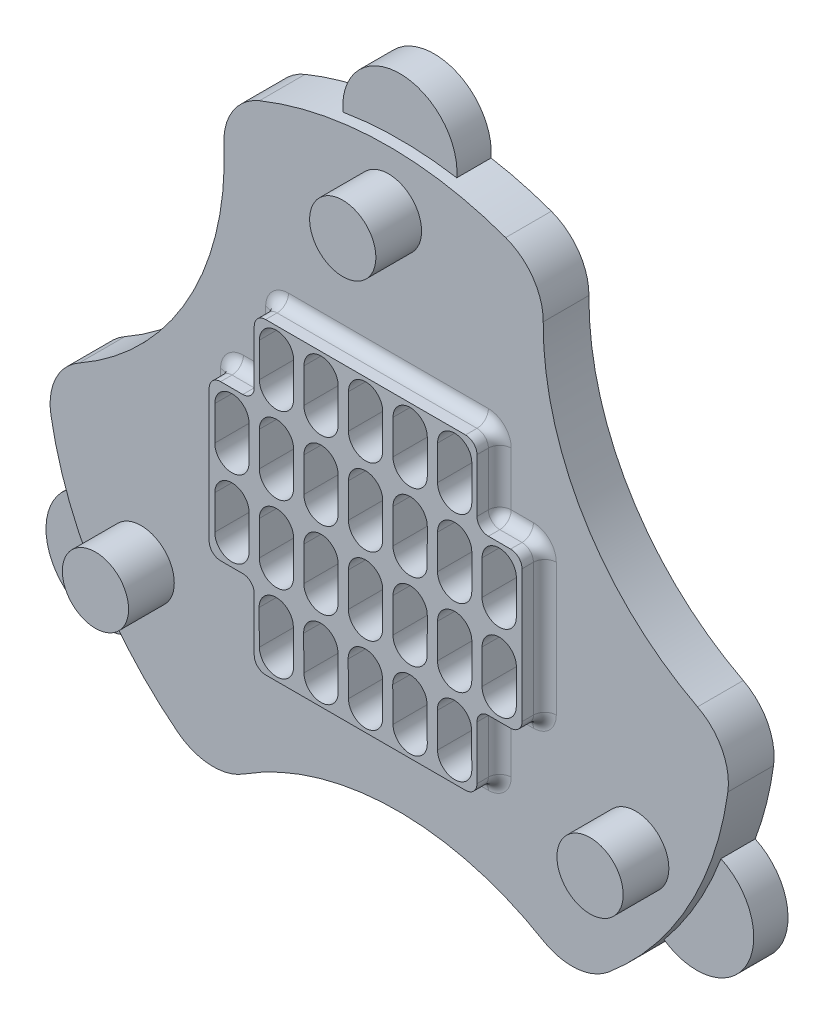
SolidWorks part; units mm, degrees
ref_plane "Спереди" through (0, 0, 0) normal (0, 0, 1) x (1, 0, 0)
ref_plane "Сверху" through (0, 0, 0) normal (0, 1, 0) x (1, 0, 0)
ref_plane "Справа" through (0, 0, 0) normal (1, 0, 0) x (0, 0, -1)
sketch "Sketch1" plane through (0, 0, 0) normal (0, 0, 1) x (1, 0, 0)
  line L0 (3.9, 6.755) -> (7.8, 0) construction
  line L2 (5.85, 10.1325) -> (11.7, 0) construction
  line L4 (7.8, 13.51) -> (15.6, 0) construction
  circle A61 centre (0, 0) radius 20
  circle A131 centre (0, 0) radius 1.25
  circle A484 centre (3.9, 0) radius 1.25
  circle A485 centre (7.8, 0) radius 1.25
  circle A486 centre (11.7, 0) radius 1.25
  circle A487 centre (15.6, 0) radius 1.25
  circle A488 centre (1.95, -3.3775) radius 1.25
  circle A489 centre (3.9, -6.755) radius 1.25
  circle A490 centre (5.85, -10.1325) radius 1.25
  circle A491 centre (7.8, -13.51) radius 1.25
  circle A492 centre (-1.95, -3.3775) radius 1.25
  circle A493 centre (-3.9, -6.755) radius 1.25
  circle A494 centre (-5.85, -10.1325) radius 1.25
  circle A495 centre (-7.8, -13.51) radius 1.25
  circle A496 centre (-3.9, 0) radius 1.25
  circle A497 centre (-7.8, 0) radius 1.25
  circle A498 centre (-11.7, 0) radius 1.25
  circle A499 centre (-15.6, 0) radius 1.25
  circle A500 centre (-1.95, 3.3775) radius 1.25
  circle A501 centre (-3.9, 6.755) radius 1.25
  circle A502 centre (-5.85, 10.1325) radius 1.25
  circle A503 centre (-7.8, 13.51) radius 1.25
  circle A504 centre (1.95, 3.3775) radius 1.25
  circle A505 centre (3.9, 6.755) radius 1.25
  circle A506 centre (5.85, 10.1325) radius 1.25
  circle A507 centre (7.8, 13.51) radius 1.25
  circle A508 centre (5.85, 3.3775) radius 1.25
  circle A509 centre (7.8, 6.755) radius 1.25
  circle A510 centre (9.75, 3.3775) radius 1.25
  circle A511 centre (11.7, 6.755) radius 1.25
  circle A512 centre (9.7491, 10.1341) radius 1.25
  circle A513 centre (13.6509, 3.3759) radius 1.25
  circle A514 centre (5.85, -3.3791) radius 1.25
  circle A515 centre (9.75, -3.3791) radius 1.25
  circle A516 centre (7.8, -6.7566) radius 1.25
  circle A517 centre (11.7, -6.7566) radius 1.25
  circle A518 centre (9.7491, -10.1356) radius 1.25
  circle A519 centre (13.6509, -3.3775) radius 1.25
  circle A520 centre (-0.0013, -6.7573) radius 1.25
  circle A521 centre (1.9487, -10.1348) radius 1.25
  circle A522 centre (-1.9513, -10.1348) radius 1.25
  circle A523 centre (-0.0013, -13.5123) radius 1.25
  circle A524 centre (-3.9032, -13.5123) radius 1.25
  circle A525 centre (3.9005, -13.5123) radius 1.25
  circle A526 centre (-5.8527, -3.3791) radius 1.25
  circle A527 centre (-7.8027, -6.7566) radius 1.25
  circle A528 centre (-9.7527, -3.3791) radius 1.25
  circle A529 centre (-11.7027, -6.7566) radius 1.25
  circle A530 centre (-13.6536, -3.3775) radius 1.25
  circle A531 centre (-9.7518, -10.1356) radius 1.25
  circle A532 centre (-5.8527, 3.3775) radius 1.25
  circle A533 centre (-9.7527, 3.3775) radius 1.25
  circle A534 centre (-7.8027, 6.755) radius 1.25
  circle A535 centre (-11.7027, 6.755) radius 1.25
  circle A536 centre (-9.7518, 10.1341) radius 1.25
  circle A537 centre (-13.6536, 3.3759) radius 1.25
  circle A538 centre (-0.0014, 6.7558) radius 1.25
  circle A539 centre (-1.9514, 10.1333) radius 1.25
  circle A540 centre (1.9486, 10.1333) radius 1.25
  circle A541 centre (-0.0014, 13.5108) radius 1.25
  circle A542 centre (3.9005, 13.5108) radius 1.25
  circle A543 centre (-3.9032, 13.5108) radius 1.25
  circle A544 centre (13.65, -1.1258) radius 2.2517 construction
  circle A545 centre (11.7009, -4.5044) radius 2.2522 construction
  circle A546 centre (9.75, -7.8834) radius 2.2522 construction
  circle A547 centre (7.7987, -11.2591) radius 2.2509 construction
  circle A548 centre (13.65, -1.1258) radius 0.65
  circle A549 centre (11.7009, -4.5044) radius 0.65
  circle A550 centre (9.75, -7.8834) radius 0.65
  circle A551 centre (7.7987, -11.2591) radius 0.65
  circle A552 centre (9.75, -1.1258) radius 0.65
  circle A553 centre (7.8009, -4.5044) radius 0.65
  circle A554 centre (5.85, -7.8834) radius 0.65
  circle A555 centre (3.8987, -11.2591) radius 0.65
  circle A556 centre (5.85, -1.1258) radius 0.65
  circle A557 centre (3.9009, -4.5044) radius 0.65
  circle A558 centre (1.95, -7.8834) radius 0.65
  circle A559 centre (-0.0013, -11.2591) radius 0.65
  circle A560 centre (1.95, -1.1258) radius 0.65
  circle A561 centre (0.0009, -4.5044) radius 0.65
  circle A562 centre (-1.95, -7.8834) radius 0.65
  circle A563 centre (-3.9013, -11.2591) radius 0.65
  circle A564 centre (-1.95, -1.1258) radius 0.65
  circle A565 centre (-3.8991, -4.5044) radius 0.65
  circle A566 centre (-5.85, -7.8834) radius 0.65
  circle A567 centre (-7.8013, -11.2591) radius 0.65
  circle A568 centre (-5.85, -1.1258) radius 0.65
  circle A569 centre (-7.7991, -4.5044) radius 0.65
  circle A570 centre (-9.75, -7.8834) radius 0.65
  circle A572 centre (-9.75, -1.1258) radius 0.65
  circle A573 centre (-11.6991, -4.5044) radius 0.65
  circle A576 centre (-13.65, -1.1258) radius 0.65
  circle A587 centre (0, 2.2517) radius 2.2517 construction
  circle A588 centre (0, 2.2517) radius 0.65
  circle A589 centre (3.9, 2.2517) radius 0.65
  circle A590 centre (7.8, 2.2517) radius 0.65
  circle A591 centre (11.7, 2.2517) radius 0.65
  circle A592 centre (15.6, 2.2517) radius 0.65
  circle A593 centre (1.9491, 5.6297) radius 2.2522 construction
  circle A594 centre (1.9491, 5.6297) radius 0.65
  circle A595 centre (5.8491, 5.6297) radius 0.65
  circle A596 centre (9.7491, 5.6297) radius 0.65
  circle A597 centre (13.6491, 5.6297) radius 0.65
  circle A598 centre (3.8991, 9.0072) radius 2.2522 construction
  circle A599 centre (3.8991, 9.0072) radius 0.65
  circle A600 centre (7.7991, 9.0072) radius 0.65
  circle A601 centre (11.6991, 9.0072) radius 0.65
  circle A602 centre (5.85, 12.3842) radius 2.2517 construction
  circle A603 centre (5.85, 12.3842) radius 0.65
  circle A604 centre (9.75, 12.3842) radius 0.65
  circle A605 centre (5.85, -14.6358) radius 0.65
  circle A606 centre (1.9509, -14.6353) radius 0.65
  circle A607 centre (-1.9491, -14.6353) radius 0.65
  circle A608 centre (-5.85, -14.6358) radius 0.65
  circle A609 centre (-15.6, 2.2517) radius 0.65
  circle A610 centre (-13.65, 5.6281) radius 0.65
  circle A611 centre (-11.7, 9.0056) radius 0.65
  circle A612 centre (-9.75, 12.3842) radius 0.65
  circle A613 centre (-5.85, 12.3842) radius 0.65
  circle A614 centre (-1.95, 12.3842) radius 0.65
  circle A615 centre (1.95, 12.3842) radius 0.65
  circle A616 centre (-7.8, 9.0056) radius 0.65
  circle A617 centre (-9.75, 5.6281) radius 0.65
  circle A618 centre (-11.7, 2.2517) radius 0.65
  circle A619 centre (-3.9, 9.0056) radius 0.65
  circle A620 centre (-5.85, 5.6281) radius 0.65
  circle A621 centre (-7.8, 2.2517) radius 0.65
  circle A622 centre (0, 9.0056) radius 0.65
  circle A623 centre (-1.95, 5.6281) radius 0.65
  circle A624 centre (-3.9, 2.2517) radius 0.65
  circle A625 centre (-15.5991, -4.5044) radius 0.65
  circle A626 centre (-13.65, -7.8834) radius 0.65
  circle A627 centre (-17.55, -7.8834) radius 0.65
  circle A628 centre (-19.5013, -11.2591) radius 0.65
  circle A629 centre (-15.6013, -11.2591) radius 0.65
  circle A630 centre (-11.7013, -11.2591) radius 0.65
  point P51 (0, 0)
  point P125 (-0.0013, -0.0008)
  point P231 (0, 0)
  dimension "D1" = 5
  dimension "D3" = 6
  dimension "D5" = 8
  dimension "D7" = 4
  dimension "D11" = 4
  dimension "D2" = 6
  dimension "D6" = 5
  dimension "D8" = 3
  dimension "D9" = 2
  dimension "D4" = 1.3
  dimension "D10" = 3
ref_plane "Plane1" through (0, 0, 10) normal (0, 0, 1) x (1, 0, 0)
sketch "Sketch2" plane through (0, 0, 10) normal (0, 0, 1) x (1, 0, 0)
  line L0 (-7.8, 13.51) -> (-7.8027, 6.755) construction
  line L1 (-9.7518, 10.1341) -> (-5.85, 10.1325) construction
  line L2 (-7.8008, 11.6325) -> (-7.8019, 8.6325) construction
  line L3 (-6.3008, 11.6319) -> (-6.3019, 8.6319)
  line L4 (-9.3008, 11.6331) -> (-9.3019, 8.6331)
  line L5 (-5.4008, 11.6331) -> (-5.4019, 8.6331)
  line L6 (-2.4008, 11.6319) -> (-2.4019, 8.6319)
  line L7 (-3.9008, 11.6325) -> (-3.9019, 8.6325) construction
  line L8 (-1.5008, 11.6331) -> (-1.5019, 8.6331)
  line L9 (1.4992, 11.6319) -> (1.4981, 8.6319)
  line L10 (-0.0008, 11.6325) -> (-0.0019, 8.6325) construction
  line L11 (2.3992, 11.6331) -> (2.3981, 8.6331)
  line L12 (5.3992, 11.6319) -> (5.3981, 8.6319)
  line L13 (3.8992, 11.6325) -> (3.8981, 8.6325) construction
  line L14 (6.2992, 11.6331) -> (6.2981, 8.6331)
  line L15 (9.2992, 11.6319) -> (9.2981, 8.6319)
  line L16 (7.7992, 11.6325) -> (7.7981, 8.6325) construction
  line L17 (-9.7518, 10.1341) -> (-9.7527, 3.3775) construction
  line L18 (-11.7027, 6.755) -> (-7.8027, 6.755) construction
  line L19 (-10.2035, 1.8767) -> (-10.202, 4.8767)
  line L22 (-9.7527, 3.3775) -> (-5.8527, 3.3775) construction
  line L25 (-7.8027, 6.755) -> (-7.8, 0) construction
  line L26 (-7.8035, 1.8775) -> (-7.8019, 4.8775) construction
  line L27 (-9.3035, 1.8782) -> (-9.3019, 4.8782)
  line L28 (-6.3035, 1.8767) -> (-6.3019, 4.8767)
  line L29 (-2.4035, 1.8767) -> (-2.4019, 4.8767)
  line L30 (-5.4035, 1.8782) -> (-5.4019, 4.8782)
  line L31 (-3.9035, 1.8775) -> (-3.9019, 4.8775) construction
  line L32 (1.4965, 1.8767) -> (1.4981, 4.8767)
  line L33 (-1.5035, 1.8782) -> (-1.5019, 4.8782)
  line L34 (-0.0035, 1.8775) -> (-0.0019, 4.8775) construction
  line L35 (5.3965, 1.8767) -> (5.3981, 4.8767)
  line L36 (2.3965, 1.8782) -> (2.3981, 4.8782)
  line L37 (3.8965, 1.8775) -> (3.8981, 4.8775) construction
  line L38 (9.2965, 1.8767) -> (9.2981, 4.8767)
  line L39 (6.2965, 1.8782) -> (6.2981, 4.8782)
  line L40 (7.7965, 1.8775) -> (7.7981, 4.8775) construction
  line L41 (13.1965, 1.8767) -> (13.1981, 4.8767)
  line L42 (10.1965, 1.8782) -> (10.1981, 4.8782)
  line L43 (11.6965, 1.8775) -> (11.6981, 4.8775) construction
  line L44 (-13.2035, 1.8782) -> (-13.2019, 4.8782)
  line L45 (-11.7035, 1.8775) -> (-11.702, 4.8775) construction
  line L46 (-9.7527, -3.3791) -> (-5.8527, -3.3791) construction
  line L47 (-7.8, 0) -> (-7.8027, -6.7566) construction
  line L48 (-7.8046, -4.8791) -> (-7.8008, -1.8791) construction
  line L49 (-9.3046, -4.8771) -> (-9.3007, -1.8771)
  line L50 (-6.3047, -4.881) -> (-6.3008, -1.881)
  line L51 (-2.4047, -4.881) -> (-2.4008, -1.881)
  line L52 (-5.4046, -4.8771) -> (-5.4007, -1.8771)
  line L53 (-3.9046, -4.8791) -> (-3.9008, -1.8791) construction
  line L54 (1.4953, -4.881) -> (1.4992, -1.881)
  line L55 (-1.5046, -4.8771) -> (-1.5007, -1.8771)
  line L56 (-0.0046, -4.8791) -> (-0.0008, -1.8791) construction
  line L57 (5.3953, -4.881) -> (5.3992, -1.881)
  line L58 (2.3954, -4.8771) -> (2.3993, -1.8771)
  line L59 (3.8954, -4.8791) -> (3.8992, -1.8791) construction
  line L60 (9.2953, -4.881) -> (9.2992, -1.881)
  line L61 (6.2954, -4.8771) -> (6.2993, -1.8771)
  line L62 (7.7954, -4.8791) -> (7.7992, -1.8791) construction
  line L63 (13.1953, -4.881) -> (13.1992, -1.881)
  line L64 (10.1954, -4.8771) -> (10.1993, -1.8771)
  line L65 (11.6954, -4.8791) -> (11.6992, -1.8791) construction
  line L66 (-10.2047, -4.881) -> (-10.2008, -1.881)
  line L67 (-13.2046, -4.8771) -> (-13.2007, -1.8771)
  line L68 (-11.7046, -4.8791) -> (-11.7008, -1.8791) construction
  line L69 (-9.7518, -10.1356) -> (-5.482, -10.1356) construction
  line L70 (-7.8027, -6.7566) -> (-7.8, -13.51) construction
  line L71 (-7.8259, -8.6356) -> (-7.8007, -11.6356) construction
  line L72 (-6.3259, -8.623) -> (-6.3008, -11.623)
  line L73 (-9.3258, -8.6482) -> (-9.3007, -11.6482)
  line L74 (-5.4258, -8.6482) -> (-5.4007, -11.6482)
  line L75 (-2.4259, -8.623) -> (-2.4008, -11.623)
  line L76 (-3.9259, -8.6356) -> (-3.9007, -11.6356) construction
  line L77 (-1.5258, -8.6482) -> (-1.5007, -11.6482)
  line L78 (1.4741, -8.623) -> (1.4992, -11.623)
  line L79 (-0.0259, -8.6356) -> (-0.0007, -11.6356) construction
  line L80 (2.3742, -8.6482) -> (2.3993, -11.6482)
  line L81 (5.3741, -8.623) -> (5.3992, -11.623)
  line L82 (3.8741, -8.6356) -> (3.8993, -11.6356) construction
  line L83 (6.2742, -8.6482) -> (6.2993, -11.6482)
  line L84 (9.2741, -8.623) -> (9.2992, -11.623)
  line L85 (7.7741, -8.6356) -> (7.7993, -11.6356) construction
  arc A0 (-6.3008, 11.6319) -> (-9.3008, 11.6331) centre (-7.8008, 11.6325) ccw
  arc A1 (-9.3019, 8.6331) -> (-6.3019, 8.6319) centre (-7.8019, 8.6325) ccw
  arc A2 (-2.4008, 11.6319) -> (-5.4008, 11.6331) centre (-3.9008, 11.6325) ccw
  arc A3 (-5.4019, 8.6331) -> (-2.4019, 8.6319) centre (-3.9019, 8.6325) ccw
  arc A4 (1.4992, 11.6319) -> (-1.5008, 11.6331) centre (-0.0008, 11.6325) ccw
  arc A5 (-1.5019, 8.6331) -> (1.4981, 8.6319) centre (-0.0019, 8.6325) ccw
  arc A6 (5.3992, 11.6319) -> (2.3992, 11.6331) centre (3.8992, 11.6325) ccw
  arc A7 (2.3981, 8.6331) -> (5.3981, 8.6319) centre (3.8981, 8.6325) ccw
  arc A8 (9.2992, 11.6319) -> (6.2992, 11.6331) centre (7.7992, 11.6325) ccw
  arc A9 (6.2981, 8.6331) -> (9.2981, 8.6319) centre (7.7981, 8.6325) ccw
  arc A14 (-9.3035, 1.8782) -> (-6.3035, 1.8767) centre (-7.8035, 1.8775) ccw
  arc A15 (-6.3019, 4.8767) -> (-9.3019, 4.8782) centre (-7.8019, 4.8775) ccw
  arc A16 (-5.4035, 1.8782) -> (-2.4035, 1.8767) centre (-3.9035, 1.8775) ccw
  arc A17 (-2.4019, 4.8767) -> (-5.4019, 4.8782) centre (-3.9019, 4.8775) ccw
  arc A18 (-1.5035, 1.8782) -> (1.4965, 1.8767) centre (-0.0035, 1.8775) ccw
  arc A19 (1.4981, 4.8767) -> (-1.5019, 4.8782) centre (-0.0019, 4.8775) ccw
  arc A20 (2.3965, 1.8782) -> (5.3965, 1.8767) centre (3.8965, 1.8775) ccw
  arc A21 (5.3981, 4.8767) -> (2.3981, 4.8782) centre (3.8981, 4.8775) ccw
  arc A22 (6.2965, 1.8782) -> (9.2965, 1.8767) centre (7.7965, 1.8775) ccw
  arc A23 (9.2981, 4.8767) -> (6.2981, 4.8782) centre (7.7981, 4.8775) ccw
  arc A24 (10.1965, 1.8782) -> (13.1965, 1.8767) centre (11.6965, 1.8775) ccw
  arc A25 (13.1981, 4.8767) -> (10.1981, 4.8782) centre (11.6981, 4.8775) ccw
  arc A26 (-13.2035, 1.8782) -> (-10.2035, 1.8767) centre (-11.7035, 1.8775) ccw
  arc A27 (-10.202, 4.8767) -> (-13.2019, 4.8782) centre (-11.702, 4.8775) ccw
  arc A28 (-9.3046, -4.8771) -> (-6.3047, -4.881) centre (-7.8046, -4.8791) ccw
  arc A29 (-6.3008, -1.881) -> (-9.3007, -1.8771) centre (-7.8008, -1.8791) ccw
  arc A30 (-5.4046, -4.8771) -> (-2.4047, -4.881) centre (-3.9046, -4.8791) ccw
  arc A31 (-2.4008, -1.881) -> (-5.4007, -1.8771) centre (-3.9008, -1.8791) ccw
  arc A32 (-1.5046, -4.8771) -> (1.4953, -4.881) centre (-0.0046, -4.8791) ccw
  arc A33 (1.4992, -1.881) -> (-1.5007, -1.8771) centre (-0.0008, -1.8791) ccw
  arc A34 (2.3954, -4.8771) -> (5.3953, -4.881) centre (3.8954, -4.8791) ccw
  arc A35 (5.3992, -1.881) -> (2.3993, -1.8771) centre (3.8992, -1.8791) ccw
  arc A36 (6.2954, -4.8771) -> (9.2953, -4.881) centre (7.7954, -4.8791) ccw
  arc A37 (9.2992, -1.881) -> (6.2993, -1.8771) centre (7.7992, -1.8791) ccw
  arc A38 (10.1954, -4.8771) -> (13.1953, -4.881) centre (11.6954, -4.8791) ccw
  arc A39 (13.1992, -1.881) -> (10.1993, -1.8771) centre (11.6992, -1.8791) ccw
  arc A40 (-13.2046, -4.8771) -> (-10.2047, -4.881) centre (-11.7046, -4.8791) ccw
  arc A41 (-10.2008, -1.881) -> (-13.2007, -1.8771) centre (-11.7008, -1.8791) ccw
  arc A42 (-6.3259, -8.623) -> (-9.3258, -8.6482) centre (-7.8259, -8.6356) ccw
  arc A43 (-9.3007, -11.6482) -> (-6.3008, -11.623) centre (-7.8007, -11.6356) ccw
  arc A44 (-2.4259, -8.623) -> (-5.4258, -8.6482) centre (-3.9259, -8.6356) ccw
  arc A45 (-5.4007, -11.6482) -> (-2.4008, -11.623) centre (-3.9007, -11.6356) ccw
  arc A46 (1.4741, -8.623) -> (-1.5258, -8.6482) centre (-0.0259, -8.6356) ccw
  arc A47 (-1.5007, -11.6482) -> (1.4992, -11.623) centre (-0.0007, -11.6356) ccw
  arc A48 (5.3741, -8.623) -> (2.3742, -8.6482) centre (3.8741, -8.6356) ccw
  arc A49 (2.3993, -11.6482) -> (5.3992, -11.623) centre (3.8993, -11.6356) ccw
  arc A50 (9.2741, -8.623) -> (6.2742, -8.6482) centre (7.7741, -8.6356) ccw
  arc A51 (6.2993, -11.6482) -> (9.2992, -11.623) centre (7.7993, -11.6356) ccw
  circle A52 centre (0, 0) radius 16.85 construction
  circle A53 centre (0, 0) radius 18.85
  point P10 (-7.8014, 10.1325)
  point P18 (-3.9014, 10.1325)
  point P25 (-0.0014, 10.1325)
  point P32 (3.8986, 10.1325)
  point P39 (7.7986, 10.1325)
  point P50 (-11.7027, 3.3775)
  point P58 (-7.8027, 3.3775)
  point P68 (-3.9027, 3.3775)
  point P75 (-0.0027, 3.3775)
  point P82 (3.8973, 3.3775)
  point P89 (7.7973, 3.3775)
  point P96 (11.6973, 3.3775)
  point P108 (-7.8027, -3.3791)
  point P116 (-3.9027, -3.3791)
  point P123 (-0.0027, -3.3791)
  point P130 (3.8973, -3.3791)
  point P137 (7.7973, -3.3791)
  point P144 (11.6973, -3.3791)
  point P151 (-11.7027, -3.3791)
  point P162 (-7.8133, -10.1356)
  point P170 (-3.9133, -10.1356)
  point P177 (-0.0133, -10.1356)
  point P184 (3.8867, -10.1356)
  point P191 (7.7867, -10.1356)
  dimension "D1" = 3
  dimension "D15" = 2
  dimension "D2" = 3
  dimension "D4" = 2
  dimension "D5" = 3
  dimension "D6" = 3
  dimension "D7" = 3
  dimension "D9" = 3
  dimension "D12" = 3
  dimension "D13" = 3
  dimension "D3" = 5
  dimension "D8" = 6
  dimension "D10" = 6
  dimension "D11" = 2
  dimension "D14" = 5
extrude "Boss-Extrude1" add sketch "Sketch2" along normal blind 4
sketch "Sketch3" plane through (0, 0, 14) normal (0, 0, 1) x (1, 0, 0)
  circle A0 centre (0, 0) radius 17.6
  circle A1 centre (0, 0) radius 30
extrude "Boss-Extrude2" add sketch "Sketch3" against normal blind 4
sketch "Sketch4" plane through (0, 0, 14) normal (0, 0, 1) x (1, 0, 0)
  circle A0 centre (0, 0) radius 25 construction
  circle A1 centre (0, 25) radius 2.9
  circle A2 centre (21.6506, -12.5) radius 2.9
  circle A3 centre (-21.6506, -12.5) radius 2.9
  point P11 (0, 0)
  dimension "D1" = 3
extrude "Boss-Extrude3" add sketch "Sketch4" along normal blind 4 and the other way blind 4
sketch "Sketch6" plane through (0, 0, 10) normal (0, 0, -1) x (-1, 0, 0)
  circle A0 centre (0, 30) radius 5
  circle A1 centre (0, 0) radius 30 construction
  circle A2 centre (25.9808, -15) radius 5
  circle A3 centre (-25.9808, -15) radius 5
  point P10 (0, 0)
  dimension "D1" = 3
extrude "Boss-Extrude4" add sketch "Sketch6" against normal blind 3
sketch "Sketch5" plane through (0, 0, 10) normal (0, 0, -1) x (-1, 0, 0)
  circle A0 centre (0, 25) radius 3
  circle A1 centre (21.6506, -12.5) radius 3
  circle A2 centre (-21.6506, -12.5) radius 3
sketch "Sketch7" plane through (0, 0, 10) normal (0, 0, -1) x (-1, 0, 0)
  line L0 (0, 0) -> (-38.5501, 23.214) construction
  circle A0 centre (0, 0) radius 45 construction
  circle A1 centre (-38.5501, 23.214) radius 25
  circle A2 centre (39.379, 21.7783) radius 25
  circle A3 centre (-0.8289, -44.9924) radius 25
  circle A4 centre (0, 0) radius 19 construction
  point P11 (0, 0)
  dimension "D1" = 3
extrude "Cut-Extrude2" cut sketch "Sketch7" against normal blind 4
fillet "Fillet1" radius 5 6 edges at (-14.7586, 26.1186, 12) (-29.9681, -1.3827, 12) (-15.2401, -25.8407, 12) (16.1815, -25.2618, 12) (29.9987, -0.278, 12) (13.7866, 26.6445, 12)
extrude "Boss-Extrude5" add sketch "Sketch2<2>" along normal blind 6
sketch "Sketch2<2>" plane through (0, 0, 10) normal (0, 0, 1) x (1, 0, 0) same geometry as "Sketch2"
sketch "Sketch8" plane through (0, 0, 16) normal (0, 0, 1) x (1, 0, 0)
  line L0 (0, 0) -> (6.0128, 0) construction
  line L1 (-9.7495, -6.7926) -> (9.7495, -6.7926)
  line L2 (0, 0) -> (0, 5.1095) construction
  line L3 (-9.7495, 13.4736) -> (9.7495, 13.4736)
  line L4 (-9.7495, 13.4736) -> (-9.7495, 6.7926)
  line L5 (-9.7495, 6.7926) -> (9.7495, 6.7926)
  line L6 (9.7495, 13.4736) -> (9.7495, 6.7926)
  line L7 (-9.7495, 13.4736) -> (9.7495, 6.7926) construction
  line L8 (-9.7495, 6.7926) -> (9.7495, 13.4736) construction
  line L9 (-13.6953, -6.7926) -> (13.6953, -6.7926)
  line L10 (-13.6953, -6.7926) -> (-13.6953, 6.7926)
  line L11 (-13.6953, 6.7926) -> (13.6953, 6.7926)
  line L12 (13.6953, -6.7926) -> (13.6953, 6.7926)
  line L13 (-13.6953, -6.7926) -> (13.6953, 6.7926) construction
  line L14 (-13.6953, 6.7926) -> (13.6953, -6.7926) construction
  line L15 (9.7495, -13.4736) -> (9.7495, -6.7926)
  line L16 (-9.7495, -13.4736) -> (9.7495, -13.4736)
  line L17 (-9.7495, -13.4736) -> (-9.7495, -6.7926)
  circle A0 centre (0, 0) radius 20.5111
  point P3 (0, 10.1331)
extrude "Cut-Extrude3" cut sketch "Sketch8" against normal blind 2 contours A0 L16 L17 L9 L10 L11 L4 L3 L6 L12 L15 region at (-19.9309, 0, 16)
fillet "Fillet2" radius 1 12 edges at (9.7495, 13.4736, 15) (9.7495, 6.7926, 15) (13.6953, 6.7926, 15) (13.6953, -6.7926, 15) (9.7495, -6.7926, 15) (9.7495, -13.4736, 15) (-9.7495, -13.4736, 15) (-9.7495, -6.7926, 15) (-13.6953, -6.7926, 15) (-13.6953, 6.7926, 15) (-9.7495, 6.7926, 15) (-9.7495, 13.4736, 15)
fillet "Fillet3" radius 1 24 edges at (-9.4566, 13.1807, 14) (0, 13.4736, 14) (9.4566, 13.1807, 14) (9.7495, 10.1331, 14) (10.0424, 7.0855, 14) (11.7224, 6.7926, 14) (13.4024, 6.4997, 14) (13.6953, 0, 14) (13.4024, -6.4997, 14) (11.7224, -6.7926, 14) (10.0424, -7.0855, 14) (9.7495, -10.1331, 14) (9.4566, -13.1807, 14) (0, -13.4736, 14) (-9.4566, -13.1807, 14) (-9.7495, -10.1331, 14) (-10.0424, -7.0855, 14) (-11.7224, -6.7926, 14) (-13.4024, -6.4997, 14) (-13.6953, 0, 14) (-13.4024, 6.4997, 14) (-11.7224, 6.7926, 14) (-10.0424, 7.0855, 14) (-9.7495, 10.1331, 14)
